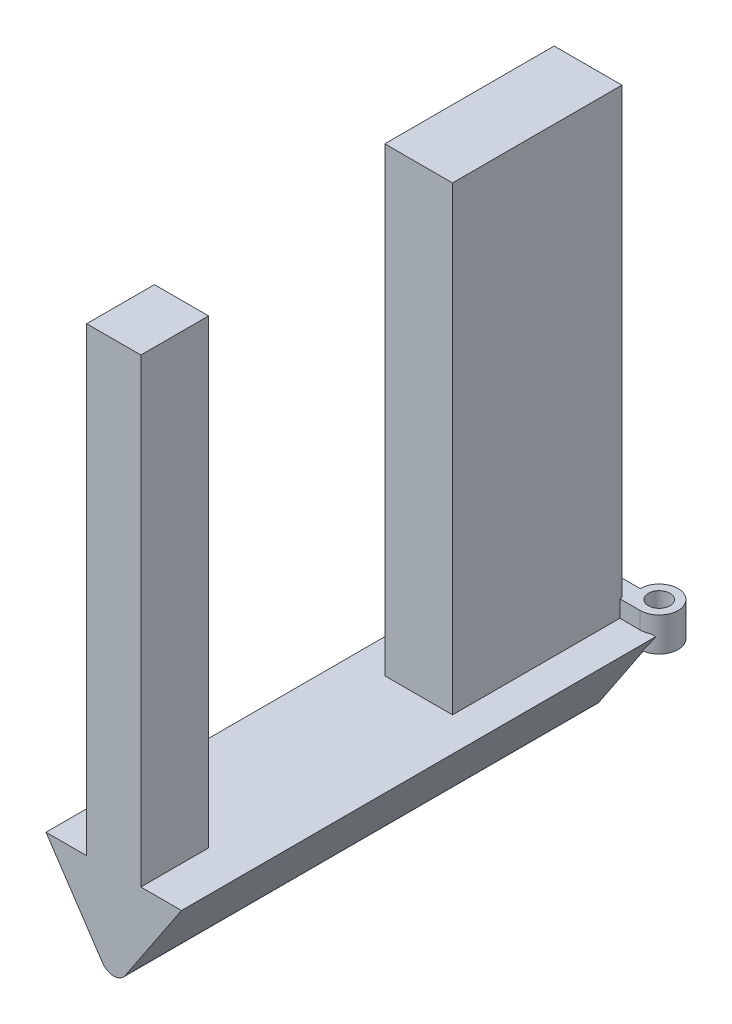
SolidWorks part; units mm, degrees
ref_plane "前视基准面" through (0, 0, 0) normal (0, 0, 1) x (1, 0, 0)
ref_plane "上视基准面" through (0, 0, 0) normal (0, 1, 0) x (1, 0, 0)
ref_plane "右视基准面" through (0, 0, 0) normal (1, 0, 0) x (0, 0, -1)
sketch "草图1" plane through (0, 0, 0) normal (0, 0, 1) x (1, 0, 0)
  line L0 (0, -15) -> (10, 0)
  line L1 (10, 0) -> (-10, 0)
  line L2 (-10, 0) -> (0, -15)
  line L3 (0, 23.0028) -> (0, 0) construction
  point P4 (0, 0)
extrude "凸台-拉伸1" add sketch "草图1" along normal blind 70
sketch "草图2" plane through (0, 0, 0) normal (0, 0, 1) x (1, 0, 0)
  line L0 (0, 0) -> (0, 8) construction
  line L1 (0, 8) -> (-5, 8) construction
  line L3 (5, 0) -> (-5, 0)
  line L4 (5, 0) -> (5, 8)
  line L5 (5, 8) -> (-5, 8)
  line L6 (-5, 0) -> (-5, 8)
  line L7 (5, 0) -> (-5, 8) construction
  line L8 (5, 8) -> (-5, 0) construction
  point P3 (0, 4)
extrude "凸台-拉伸2" add sketch "草图2" along normal blind 25
sketch "草图3" plane through (0, 0, 70) normal (0, 0, 1) x (1, 0, 0)
  line L0 (0, 0) -> (0, 8) construction
  line L1 (5, 8) -> (-5, 8) construction
  line L3 (4, 0) -> (-4, 0)
  line L4 (4, 0) -> (4, 8)
  line L5 (4, 8) -> (-4, 8)
  line L6 (-4, 0) -> (-4, 8)
  line L7 (4, 0) -> (-4, 8) construction
  line L8 (4, 8) -> (-4, 0) construction
  point P5 (0, 4)
extrude "凸台-拉伸3" add sketch "草图3" against normal blind 10
sketch "草图5" plane through (0, 0, 0) normal (0, -1, 0) x (1, 0, 0)
  line L0 (-5.2, -2.5) -> (5.2, -2.5)
  line L2 (0, 0) -> (0, -7.3568) construction
  line L3 (-8, 0.3) -> (8, 0.3)
  circle A0 centre (-8, -2.5) radius 1.6
  arc A1 (-8, 0.3) -> (-5.2, -2.5) centre (-8, -2.5) ccw
  arc A2 (8, 0.3) -> (5.2, -2.5) centre (8, -2.5) cw
  circle A3 centre (8, -2.5) radius 1.6
extrude "凸台-拉伸4" add sketch "草图5" against normal mid plane 5
fillet "圆角1" radius 2 1 edges at (0, -15, 35)
sketch "草图6" plane through (0, 8, 0) normal (0, 1, 0) x (1, 0, 0)
  line L4 (5, 0) -> (-5, 0)
  line L5 (-5, 0) -> (-5, -25)
  line L6 (-5, -25) -> (5, -25)
  line L7 (5, -25) -> (5, 0)
  line L8 (5, 0) -> (-5, 0)
  line L9 (-5, 0) -> (-5, -25)
  line L10 (-5, -25) -> (5, -25)
  line L11 (5, -25) -> (5, 0)
  dimension "D1" = 0
extrude "凸台-拉伸5" add sketch "草图6" along normal blind 60
sketch "草图7" plane through (0, 8, 0) normal (0, 1, 0) x (1, 0, 0)
  line L4 (-4, -70) -> (4, -70)
  line L5 (4, -70) -> (4, -60)
  line L6 (4, -60) -> (-4, -60)
  line L7 (-4, -60) -> (-4, -70)
  line L8 (-4, -70) -> (4, -70)
  line L9 (4, -70) -> (4, -60)
  line L10 (4, -60) -> (-4, -60)
  line L11 (-4, -60) -> (-4, -70)
  dimension "D1" = 0
extrude "凸台-拉伸6" add sketch "草图7" along normal blind 60
